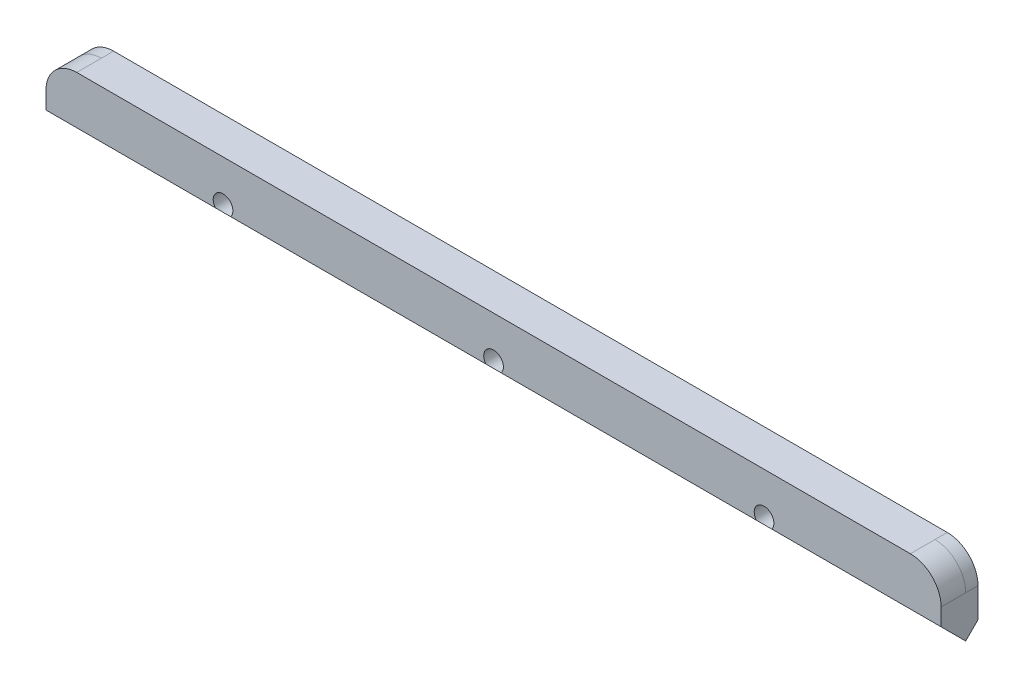
SolidWorks part; units mm, degrees
material "6061-T6 (SS)"
ref_plane "Front Plane" through (0, 0, 0) normal (0, 0, 1) x (1, 0, 0)
ref_plane "Top Plane" through (0, 0, 0) normal (0, 1, 0) x (1, 0, 0)
ref_plane "Right Plane" through (0, 0, 0) normal (1, 0, 0) x (0, 0, -1)
sketch "Sketch1" plane through (0, 0, 0) normal (1, 0, 0) x (0, 0, -1)
  line L0 (-3.0983, 0) -> (1.226, 0) construction
  line L1 (0, -3.2) -> (-2, -1.2)
  line L2 (0, -3.2) -> (0, 3.2)
  line L4 (-2, -1.2) -> (-2, 3.2)
  line L5 (-2, 3.2) -> (0, 3.2)
  dimension "D1" = 2
  dimension "D2" = 45
  dimension "D3" = 6.4
extrude "Boss-Extrude1" add sketch "Sketch1" along normal mid plane 72.8
sketch "Sketch4" [suppressed] plane through (0, 0, 0) normal (0, 0, 1) x (1, 0, 0)
  line L1 (7.5, 1.5) -> (-7.5, 1.5)
  line L2 (7.5, 1.5) -> (7.5, -3.2)
  line L3 (7.5, -3.2) -> (-7.5, -3.2)
  line L4 (-7.5, 1.5) -> (-7.5, -3.2)
  line L5 (0, 7.7759) -> (0, -8.8374) construction
  line L8 (-7.5, -3.2) -> (-7.5, 0.8) construction
  dimension "D1" = 4.7
extrude "Cut-Extrude4" [suppressed] cut sketch "Sketch4" along normal through all
fillet "Fillet3" radius 2.5 2 edges at (-36.4, 3.2, 1) (36.4, 3.2, 1)
sketch "Sketch5" plane through (-36.4, 0, 0) normal (-1, 0, 0) x (0, 0, 1)
  line L0 (0, -2.7) -> (2, -0.7)
  line L1 (0, -3.2) -> (0, 0.7) construction
  line L2 (2, 0.7) -> (2, -1.2) construction
  line L3 (2, -1.2) -> (0, -3.2) construction
  line L4 (2, -1.2) -> (2, -0.7)
  line L5 (2, -1.2) -> (0, -3.2)
  line L6 (0, -3.2) -> (0, -2.7)
  dimension "D1" = 0.5
extrude "Cut-Extrude5" cut sketch "Sketch5" against normal up to surface (72.8 mm away) up to face at (36.4, -0.75, 1)
sketch "Sketch6" [suppressed] plane through (-36.4, 0, 0) normal (-1, 0, 0) x (0, 0, 1)
  line L0 (2, -0.4929) -> (0, -2.4929)
  line L1 (2, 0.7) -> (2, -1.2) construction
  line L2 (0, -3.2) -> (0, 0.7) construction
  line L3 (2, -1.2) -> (0, -3.2) construction
  line L4 (2, -0.4929) -> (2, -1.2)
  line L5 (2, -1.2) -> (0, -3.2)
  line L6 (0, -3.2) -> (0, -2.4929)
  dimension "D1" = 0.5
extrude "Cut-Extrude6" [suppressed] cut sketch "Sketch6" against normal up to surface (72.8 mm away) up to face at (36.4, -0.5, 1)
sketch "Sketch7" plane through (-36.4, 0, 0) normal (-1, 0, 0) x (0, 0, 1)
  line L0 (0, -2.7) -> (-1, -1.7)
  line L1 (-1, -1.7) -> (-1, 3.2)
  line L2 (-1, 3.2) -> (0, 3.2)
  line L3 (0, 3.2) -> (0, -2.7)
  line L4 (0, 3.2) -> (2, 3.2) construction
  dimension "D1" = 45
  dimension "D2" = 3
extrude "Boss-Extrude2" add sketch "Sketch7" against normal up to surface (72.8 mm away) up to face at (36.4, -0.5, 1)
hole_wizard "M2x0.4 Tapped Hole1" positions "Sketch2" profile "Sketch3" tap size "M2x0.4" standard "ANSI Metric"
sketch "Sketch2" plane through (0, 0, 2) normal (0, 0, 1) x (1, 0, 0)
  circle A4 centre (-22, -0.2) radius 1.2 construction
  circle A5 centre (-22, -0.2) radius 1.2
  circle A6 centre (0, -0.2) radius 1.2 construction
  circle A7 centre (0, -0.2) radius 1.2
  circle A8 centre (22, -0.2) radius 1.2 construction
  circle A9 centre (22, -0.2) radius 1.2
  point P22 (-22, -0.2)
  point P25 (0, -0.2)
  point P28 (22, -0.2)
cosmetic thread "Hole Thread4" parameters "D1"=2, "D2"=2
cosmetic thread "Hole Thread5" parameters "D1"=2, "D2"=2
cosmetic thread "Hole Thread6" parameters "D1"=2, "D2"=2
sketch "Sketch3" plane through (-22, -0.2, 2) normal (1, 0, 0) x (0, -1, 0)
  line L0 (0, 0) -> (0, 4.0807)
  line L1 (0, 4.0807) -> (0.8, 3.6)
  line L2 (0.8, 3.6) -> (0.8, 0)
  line L5 (0.8, 0) -> (0, 0)
  line L10 (0, 4.0807) -> (-0.8, 3.6) construction
  line L11 (0, -6.35) -> (0, 107.95) construction
  dimension "Tap Drill Dia." = 1.6
  dimension "Tap Drill Depth" = 3.6
  dimension "Drill Angle" = 118
fillet "Fillet4" radius 2.5 2 edges at (-36.4, 3.2, -0.5) (36.4, 3.2, -0.5)
